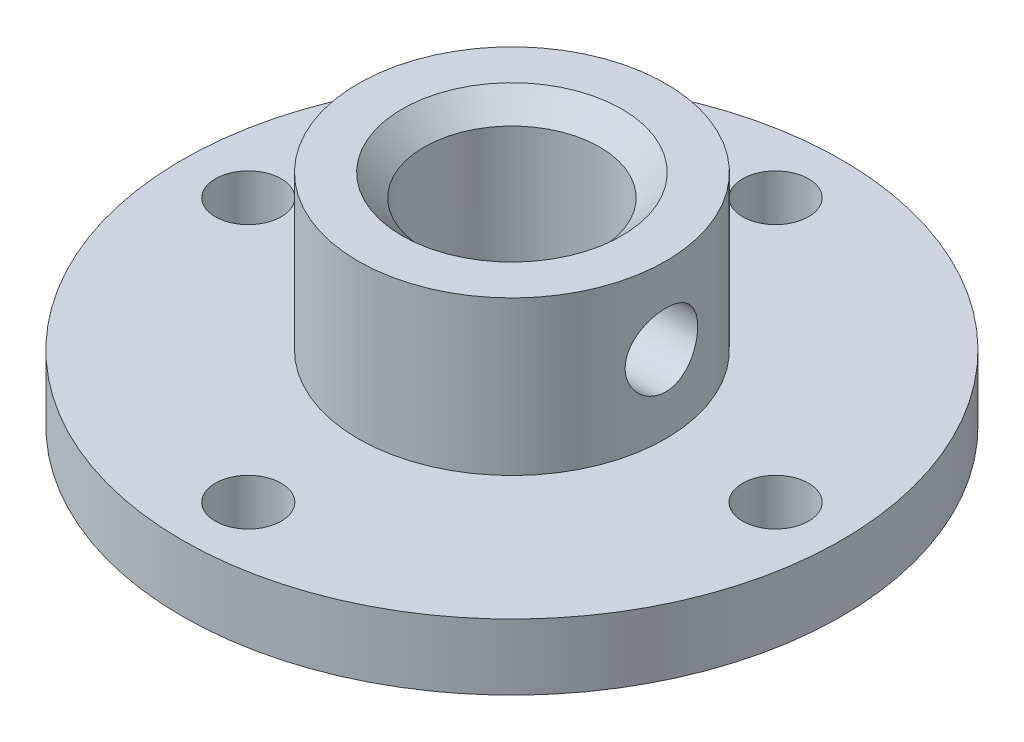
SolidWorks part; units mm, degrees
ref_plane "前视基准面" through (0, 0, 0) normal (0, 0, 1) x (1, 0, 0)
ref_plane "上视基准面" through (0, 0, 0) normal (0, 1, 0) x (1, 0, 0)
ref_plane "右视基准面" through (0, 0, 0) normal (1, 0, 0) x (0, 0, -1)
sketch "草图1" plane through (0, 0, 0) normal (0, 1, 0) x (1, 0, 0)
  circle A0 centre (0, 0) radius 15
  circle A1 centre (0, 0) radius 4
  dimension "D1" = 30
  dimension "D2" = 8
extrude "凸台-拉伸1" add sketch "草图1" along normal blind 3 contours A1 | A0 region at (0, 0, 0)
sketch "草图2" plane through (0, 3, 0) normal (0, 1, 0) x (1, 0, 0)
  circle A0 centre (0, 0) radius 4
  circle A1 centre (0, 0) radius 7
  dimension "D1" = 14
extrude "凸台-拉伸2" add sketch "草图2" along normal blind 7
ref_axis "基准轴1" through (0, 9, 0) along (0, -1, 0)
sketch "草图4" plane through (0, 0, 0) normal (0, -1, 0) x (-1, 0, 0)
  line L0 (0, 0) -> (0, -10.4165)
ref_plane "基准面1" through (0, 0, 0) normal (-1, 0, 0) x (0, 0, 1)
sketch "草图5" plane through (0, 0, 0) normal (-1, 0, 0) x (0, 0, 1)
  line L0 (7, 10) -> (-7, 10) construction
  line L1 (-7, 10) -> (-7, 3) construction
  circle A0 centre (0, 6.5) radius 1.65
  dimension "D1" = 3.3
  dimension "D2" = 3.5
  dimension "D3" = 7
extrude "切除-拉伸1" cut sketch "草图5" against normal blind 12
sketch "草图6" plane through (0, 0, 0) normal (0, -1, 0) x (1, 0, 0)
  circle A0 centre (0, 0) radius 6.5
  dimension "D1" = 13
extrude "切除-拉伸2" cut sketch "草图6" against normal blind 1.5
sketch "草图7" plane through (0, 3, 0) normal (0, 1, 0) x (1, 0, 0)
  circle A0 centre (0, -12) radius 1.5
  circle A1 centre (-12, 0) radius 1.5
  circle A2 centre (0, 12) radius 1.5
  circle A3 centre (12, 0) radius 1.5
  point P12 (0, 0)
  dimension "D1" = 0
  dimension "D2" = 12
  dimension "D3" = 3
  dimension "D4" = 4
extrude "切除-拉伸3" cut sketch "草图7" against normal blind 4 contours A3 | A0 | A1 | A2 region at (12, 3, 0)
chamfer "倒角1" distance 1 angle 45 1 edges at (0, 10, 4)
